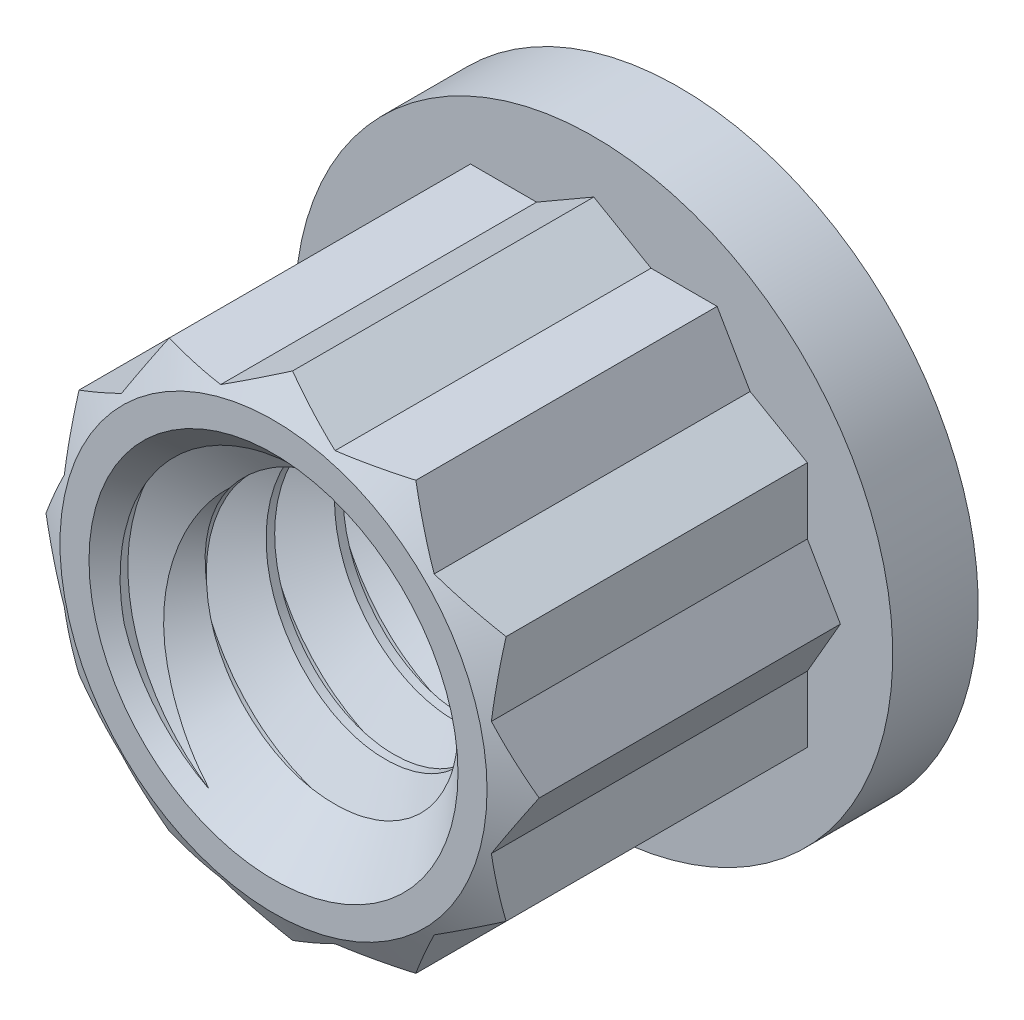
SolidWorks part; units mm, degrees
material "Plain Carbon Steel"
ref_plane "Front Plane" through (0, 0, 0) normal (0, 0, 1) x (1, 0, 0)
ref_plane "Top Plane" through (0, 0, 0) normal (0, 1, 0) x (1, 0, 0)
ref_plane "Right Plane" through (0, 0, 0) normal (1, 0, 0) x (0, 0, -1)
sketch "Sketch1" plane through (0, 0, 0) normal (0, 0, 1) x (1, 0, 0)
  line L1 (0, 4.5827) -> (-3.9688, 2.2914)
  line L2 (-3.9688, 2.2914) -> (-3.9688, -2.2914)
  line L3 (-3.9688, -2.2914) -> (0, -4.5827)
  line L4 (0, -4.5827) -> (3.9688, -2.2914)
  line L5 (3.9688, -2.2914) -> (3.9688, 2.2914)
  line L6 (3.9688, 2.2914) -> (0, 4.5827)
  circle A0 centre (0, 0) radius 3.9688 construction
  dimension "Hex" = 7.9375
extrude "Extrude1" add sketch "Sketch1" against normal blind 7.5406
sketch "Sketch14" plane through (0, 0, 0) normal (0, 0, 1) x (1, 0, 0)
  line L1 (-2.2914, 3.9688) -> (-4.5827, 0)
  line L2 (-4.5827, 0) -> (-2.2914, -3.9688)
  line L3 (-2.2914, -3.9688) -> (2.2914, -3.9688)
  line L4 (2.2914, -3.9688) -> (4.5827, 0)
  line L5 (4.5827, 0) -> (2.2914, 3.9688)
  line L6 (2.2914, 3.9688) -> (-2.2914, 3.9688)
  circle A0 centre (0, 0) radius 3.9688 construction
  circle A1 centre (0, 0) radius 3.9688 construction
extrude "Extrude4" add sketch "Sketch14" against normal up to surface (7.5406 mm away) up to face at (0, 0, -7.5406)
sketch "Sketch13" plane through (0, 0, -7.5406) normal (0, 0, -1) x (-1, 0, 0)
  circle A0 centre (0, 0) radius 5.5562
  dimension "Flange od" = 11.1125
extrude "Extrude3" add sketch "Sketch13" against normal blind 1.5875
sketch "Sketch2" plane through (0, 0, 0) normal (0, 0, 1) x (1, 0, 0)
  circle A0 centre (0, 0) radius 3.9688 construction
  circle A1 centre (0, 0) radius 3.9688
extrude "Cut-Extrude1" cut sketch "Sketch2" against normal through all draft 60 flip side to cut
sketch "Sketch4" plane through (0, 0, 0) normal (0, 0, 1) x (1, 0, 0)
  circle A0 centre (0, 0) radius 3.175
  dimension "Thread Dia" = 6.35
extrude "Cut-Extrude3" cut sketch "Sketch4" against normal through all
sketch "Sketch7" plane through (0, 0, 0) normal (0, 0, 1) x (1, 0, 0)
  circle A4 centre (0, 0) radius 3.429
  circle A5 centre (0, 0) radius 3.429
  dimension "D1" = 0.254
sketch "Sketch8" plane through (0, 0, -7.5406) normal (0, 0, -1) x (-1, 0, 0)
  circle A1 centre (0, 0) radius 3.429
  circle A2 centre (0, 0) radius 3.429 construction
sketch "Sketch5" plane through (0, 0, 0) normal (0, 0, 1) x (1, 0, 0)
  circle A0 centre (0, 0) radius 3.175 construction
  circle A1 centre (0, 0) radius 3.175
curve "Helix/Spiral1" pitch 1.27 height 8.8106 turns 6.9375 parameters "pitch"=1.27
sketch "Sketch9" plane through (0, 0, 0) normal (1, 0, 0) x (0, 0, -1)
  line L0 (-0.635, 3.175) -> (-0.4763, 3.175)
  line L1 (-0.4763, 3.175) -> (0, 2.3501)
  line L2 (-0.635, 3.175) -> (-1.1113, 2.3501)
  line L3 (-1.1113, 2.3501) -> (0, 2.3501)
  line L4 (-0.5556, 3.175) -> (-0.5556, 2.3501) construction
  line L5 (-0.8731, 2.7626) -> (-0.2381, 2.7626) construction
  line L7 (0, 2.3501) -> (0, 3.175) construction
  line L8 (0, 3.175) -> (0, -3.175) construction
  dimension "D1" = 0.1588
  dimension "D2" = 0.635
  dimension "D3" = 60
sketch "Sketch12" plane through (0, 0, 0) normal (0, 0, 1) x (1, 0, 0)
  circle A0 centre (0, 0) radius 2.3501
  circle A1 centre (0, 0) radius 3.175 construction
  circle A2 centre (0, 0) radius 3.175
extrude "Extrude2" add sketch "Sketch12" against normal up to surface (7.5406 mm away) up to face at (3.175, 0, -7.5406)
sweep "Cut-Sweep1" cut profiles "Sketch9" path "Helix/Spiral1"
extrude "Cut-Extrude6" cut sketch "Sketch7" against normal through all draft 45
extrude "Cut-Extrude7" cut sketch "Sketch8" against normal through all draft 45
equation "\"D2@Sketch9\" = \"pitch@Helix/Spiral1\"*.5"
equation "\"D3@Helix/Spiral1\" = \"pitch@Helix/Spiral1\"+\"Height@Extrude1\""
equation "\"D1@Sketch9\" = \"pitch@Helix/Spiral1\"*.125"
